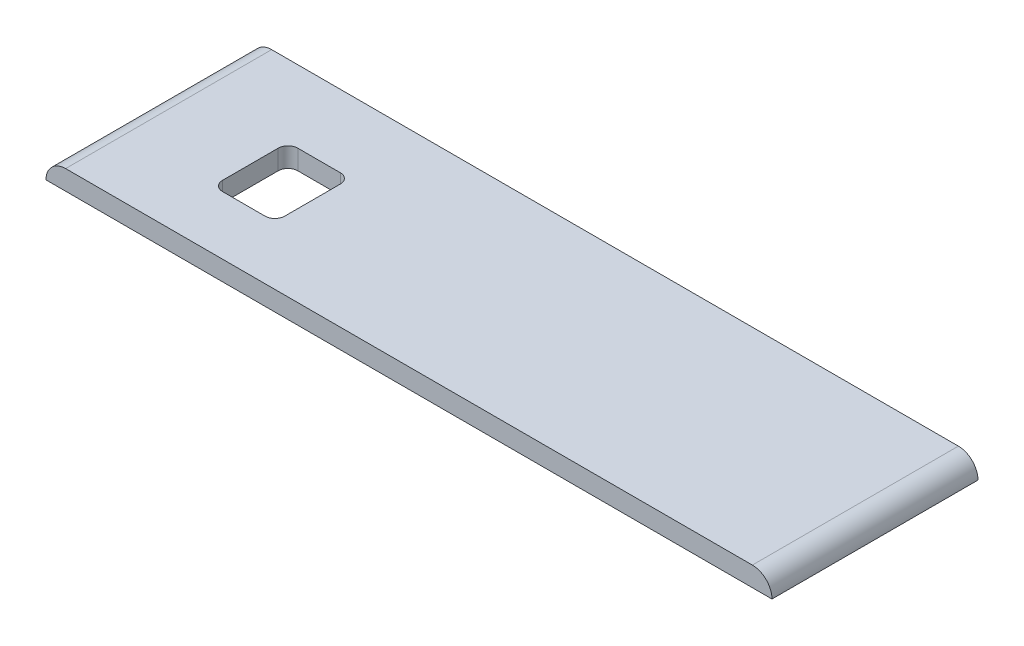
SolidWorks part; units mm, degrees
ref_plane "Спереди" through (0, 0, 0) normal (0, 0, 1) x (1, 0, 0)
ref_plane "Сверху" through (0, 0, 0) normal (0, 1, 0) x (1, 0, 0)
ref_plane "Справа" through (0, 0, 0) normal (1, 0, 0) x (0, 0, -1)
other "Configuration Table"
sketch "Эскиз1" plane through (0, 0, 0) normal (0, 1, 0) x (1, 0, 0)
  line L1 (-2, -31.5) -> (109, -31.5)
  line L2 (-2, -31.5) -> (-2, 0)
  line L3 (-2, 0) -> (109, 0)
  line L4 (109, -31.5) -> (109, 0)
  line L5 (14.55, -22.55) -> (24.05, -22.55)
  line L6 (14.55, -22.55) -> (14.55, -11.05)
  line L7 (14.55, -11.05) -> (24.05, -11.05)
  line L8 (24.05, -22.55) -> (24.05, -11.05)
extrude "Бобышка-Вытянуть1" add sketch "Эскиз1" along normal blind 3
fillet "tool_D3_R1p5_power_corners" radius 1.5 4 edges at (14.55, 1.5, 11.05) (24.05, 1.5, 11.05) (24.05, 1.5, 22.55) (14.55, 1.5, 22.55) tangent propagation no
fillet "tool_D3_R3_rear_outer_corners" radius 3 2 edges at (-2, 3, 15.75) (109, 3, 15.75)
